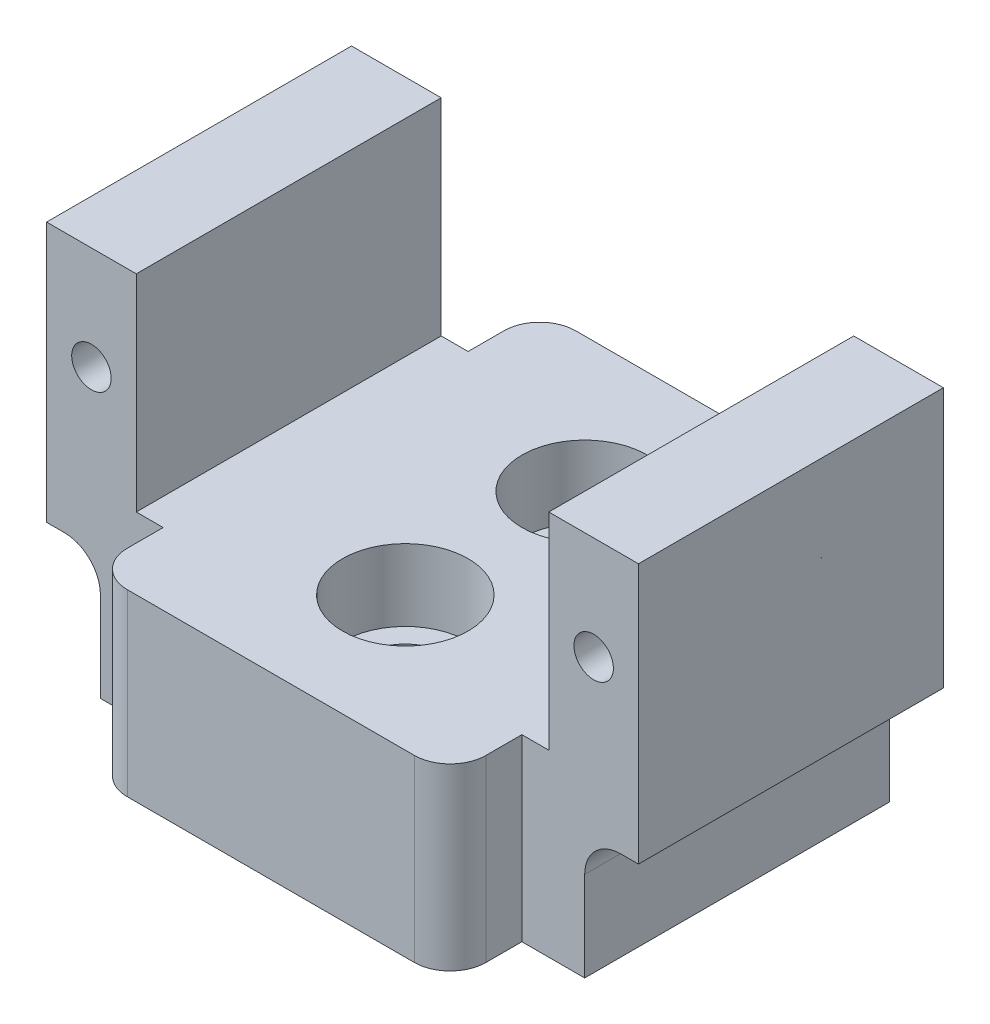
SolidWorks part; units mm, degrees
material "ABS"
ref_plane "Alzado" through (0, 0, 0) normal (0, 0, 1) x (1, 0, 0)
ref_plane "Planta" through (0, 0, 0) normal (0, 1, 0) x (1, 0, 0)
ref_plane "Vista lateral" through (0, 0, 0) normal (1, 0, 0) x (0, 0, -1)
sketch "Croquis2" plane through (0, 0, 0) normal (0, 0, 1) x (1, 0, 0)
  line L2 (0, 0) -> (0, 11.5)
  line L3 (0, 11.5) -> (5, 11.5)
  line L4 (33, 0) -> (33, 11.5)
  line L5 (5, 0) -> (5, 11.5)
  line L6 (28, 0) -> (28, 11.5)
  line L7 (28, 11.5) -> (33, 11.5)
  line L9 (0, 0) -> (0, -3)
  line L10 (0, -3) -> (33, -3)
  line L11 (33, 0) -> (33, -3)
  line L12 (5, 0) -> (28, 0)
  dimension "D1" = 33
  dimension "D2" = 11.5
  dimension "D5" = 5
  dimension "D6" = 5
  dimension "D7" = 3
extrude "Saliente-Extruir1" add sketch "Croquis2" along normal blind 17
sketch "Croquis4" plane through (0, 0, 0) normal (0, 1, 0) x (1, 0, 0)
  line L0 (16.5, -17) -> (16.5, 0) construction
  line L1 (28, -17) -> (5, -17) construction
  line L2 (28, 0) -> (5, 0) construction
  line L3 (9, -8.5) -> (16.5, -8.5) construction
  circle A0 centre (9, -8.5) radius 2.5
  circle A1 centre (24, -8.5) radius 2.5
  dimension "D1" = 5
  dimension "D2" = 7.5
extrude "Cortar-Extruir2" cut sketch "Croquis4" against normal blind 5
sketch "Croquis5" plane through (0, -3, 0) normal (0, -1, 0) x (1, 0, 0)
  line L0 (16.5, 17) -> (16.5, 0) construction
  line L1 (0, 17) -> (33, 17) construction
  line L2 (0, 0) -> (33, 0) construction
  line L4 (3, 0) -> (30, 0)
  line L5 (3, 0) -> (3, 17)
  line L6 (3, 17) -> (30, 17)
  line L7 (30, 0) -> (30, 17)
  line L8 (3, 0) -> (30, 17) construction
  line L9 (3, 17) -> (30, 0) construction
  circle A0 centre (9, 8.5) radius 2.5
  circle A1 centre (24, 8.5) radius 2.5
  point P6 (16.5, 8.5)
  dimension "D1" = 17
  dimension "D2" = 27
extrude "Saliente-Extruir4" add sketch "Croquis5" along normal blind 7
fillet "Redondeo2" radius 2 2 edges at (3, -3, 8.5) (30, -3, 8.5)
sketch "Croquis6" plane through (0, 0, 0) normal (0, 1, 0) x (1, 0, 0)
  circle A0 centre (9, -8.5) radius 3.5
  circle A1 centre (24, -8.5) radius 3.5
  dimension "D1" = 7
  dimension "D2" = 7
extrude "Cortar-Extruir3" cut sketch "Croquis6" against normal blind 1
sketch "Croquis8" plane through (0, 0, 17) normal (0, 0, 1) x (1, 0, 0)
  line L0 (2.5, 5.75) -> (2.5, 11.5) construction
  line L2 (5, 11.5) -> (0, 11.5) construction
  line L3 (2.5, 5.75) -> (0, 5.75) construction
  line L4 (0, 11.5) -> (0, -3) construction
  line L5 (16.5, 0) -> (16.5, 11.5) construction
  line L6 (28, 0) -> (5, 0) construction
  circle A0 centre (2.5, 5.75) radius 1.1
  circle A1 centre (30.5, 5.75) radius 1.1
  dimension "D2" = 2.2
  dimension "D1" = 28
  dimension "D3" = 5.75
sketch "Croquis9" plane through (0, 0, 0) normal (0, 1, 0) x (1, 0, 0)
  circle A0 centre (9, -8.5) radius 3.5
  circle A1 centre (24, -8.5) radius 3.5
extrude "Saliente-Extruir7" add sketch "Croquis9" against normal blind 10
sketch "Croquis10" plane through (0, -10, 0) normal (0, -1, 0) x (1, 0, 0)
  line L0 (16.5, 0) -> (16.5, 17) construction
  line L1 (3, 0) -> (30, 0) construction
  line L2 (30, 17) -> (3, 17) construction
  line L3 (16.5, 2.5) -> (16.5, 14.5) construction
  line L5 (6.5, 21) -> (26.5, 21)
  line L6 (6.5, 21) -> (6.5, -4)
  line L7 (6.5, -4) -> (26.5, -4)
  line L8 (26.5, 21) -> (26.5, -4)
  line L9 (6.5, 21) -> (26.5, -4) construction
  line L10 (6.5, -4) -> (26.5, 21) construction
  circle A0 centre (16.5, 14.5) radius 2.5
  circle A1 centre (16.5, 2.5) radius 2.3
  point P9 (16.5, 8.5)
  point P12 (16.5, 8.5)
  point P13 (16.5, 8.5)
  dimension "D1" = 5
  dimension "D2" = 4.6
  dimension "D3" = 12
  dimension "D4" = 25
  dimension "D5" = 20
extrude "Saliente-Extruir8" add sketch "Croquis10" against normal blind 10 contours L5 L8 L7 L6
sketch "Croquis11" plane through (0, -10, 0) normal (0, -1, 0) x (1, 0, 0)
  line L0 (16.5, 13.5) -> (16.5, 3.5) construction
  line L1 (3, 8.5) -> (30, 8.5) construction
  line L2 (3, 17) -> (3, 0) construction
  line L3 (30, 0) -> (30, 17) construction
  circle A0 centre (16.5, 13.5) radius 2.3
  circle A1 centre (16.5, 3.5) radius 2.3
  point P4 (16.5, 8.5)
  point P11 (16.5, 8.5)
  dimension "D1" = 4.6
  dimension "D2" = 4.6
  dimension "D3" = 10
extrude "Cortar-Extruir6" cut sketch "Croquis11" against normal blind 10
sketch "Croquis12" plane through (0, 0, 0) normal (0, 1, 0) x (1, 0, 0)
  circle A0 centre (16.5, -3.5) radius 3.5
  circle A1 centre (16.5, -13.5) radius 3.5
  dimension "D1" = 7
  dimension "D2" = 7
extrude "Cortar-Extruir7" cut sketch "Croquis12" against normal blind 4
fillet "Redondeo3" radius 2 4 edges at (26.5, -5, -4) (6.5, -5, -4) (6.5, -5, 21) (26.5, -5, 21)
extrude "Cortar-Extruir8" cut sketch "Croquis8" against normal through all
